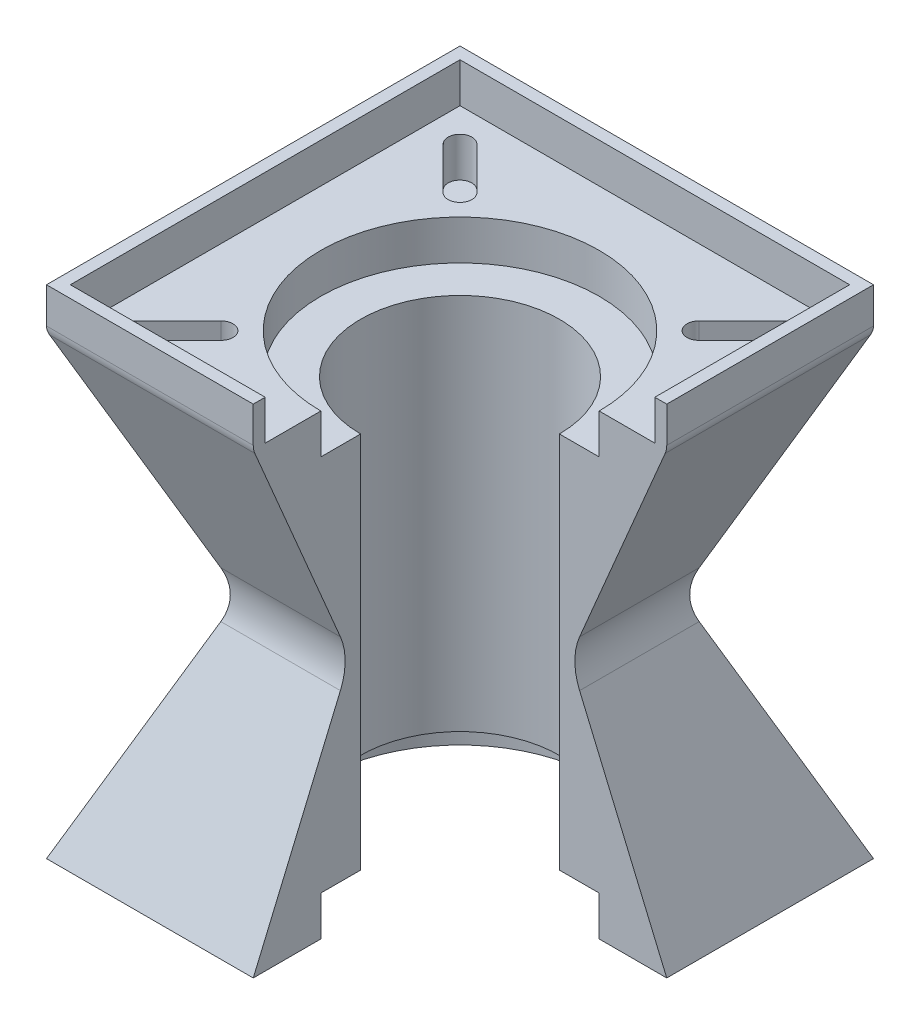
SolidWorks part; units mm, degrees
material "Cast Stainless Steel"
ref_plane "Front Plane" through (0, 0, 0) normal (0, 0, 1) x (1, 0, 0)
ref_plane "Top Plane" through (0, 0, 0) normal (0, 1, 0) x (1, 0, 0)
ref_plane "Right Plane" through (0, 0, 0) normal (1, 0, 0) x (0, 0, -1)
sketch "Sketch2" plane through (0, 0, 0) normal (0, 1, 0) x (1, 0, 0)
  line L1 (-52, -52) -> (52, -52)
  line L2 (-52, -52) -> (-52, 52)
  line L3 (-52, 52) -> (52, 52)
  line L4 (52, -52) -> (52, 52)
  line L5 (-52, -52) -> (52, 52) construction
  line L6 (-52, 52) -> (52, -52) construction
  point P0 (0, 0)
  dimension "D1" = 104
  dimension "D2" = 104
extrude "Boss-Extrude1" add sketch "Sketch2" along normal blind 57.5 draft 23
mirror "Mirror1" about plane through (0, 57.5, 0) normal (0, -1, 0) of "Boss-Extrude1"
sketch "Sketch3" plane through (0, 115, 0) normal (0, 1, 0) x (1, 0, 0)
  circle A0 centre (0, 0) radius 25
  dimension "D1" = 50
extrude "Cut-Extrude1" cut sketch "Sketch3" against normal through all
sketch "Sketch4" plane through (0, 115, 0) normal (0, 1, 0) x (1, 0, 0)
  circle A0 centre (0, 0) radius 35
  dimension "D1" = 70
extrude "Cut-Extrude2" cut sketch "Sketch4" against normal blind 10
ref_plane "Plane1" through (0, 57.5, 0) normal (0, 1, 0) x (1, 0, 0)
mirror "Mirror2" about plane through (0, 57.5, 0) normal (0, 1, 0) of "Cut-Extrude2"
sketch "Sketch6" plane through (0, 115, 0) normal (0, 1, 0) x (1, 0, 0)
  line L1 (0, 0) -> (52, 0)
  line L2 (0, 0) -> (0, -52)
  line L3 (0, -52) -> (52, -52)
  line L4 (52, 0) -> (52, -52)
extrude "Cut-Extrude3" cut sketch "Sketch6" against normal through all
fillet "Fillet1" radius 15 4 edges at (0, 57.5, -27.5927) (-27.5927, 57.5, 0) (27.5927, 57.5, -13.7963) (-13.7963, 57.5, 27.5927)
sketch "Sketch7" plane through (0, 115, 0) normal (0, 1, 0) x (1, 0, 0)
  line L6 (0, -52) -> (0, -35)
  line L7 (35, 0) -> (52, 0)
  line L8 (52, 0) -> (52, 52)
  line L9 (52, 52) -> (-52, 52)
  line L10 (-52, 52) -> (-52, -52)
  line L11 (-52, -52) -> (0, -52)
  line L12 (0, -52) -> (0, -49)
  line L14 (52, 0) -> (52, 52)
  line L15 (52, 52) -> (-52, 52)
  line L16 (-52, 52) -> (-52, -52)
  line L17 (-52, -52) -> (0, -52)
  line L18 (49, 0) -> (49, 49)
  line L19 (49, 49) -> (-49, 49)
  line L20 (-49, 49) -> (-49, -49)
  line L21 (-49, -49) -> (0, -49)
  line L22 (49, 0) -> (52, 0)
  arc A1 (35, 0) -> (0, -35) centre (0, 0) ccw
  arc A2 (35, 0) -> (0, -35) centre (0, 0) ccw
  dimension "D1" = 0
  dimension "D2" = 3
extrude "Boss-Extrude2" add sketch "Sketch7" along normal blind 10 contours L20 L21 L12 L17 L16 L15 L14 L22 L18 L19
fillet "Fillet2" radius 5 4 edges at (52, 115, -26) (0, 115, -52) (-52, 115, 0) (-26, 115, 52)
sketch "Sketch8" plane through (0, 115, 0) normal (0, 1, 0) x (1, 0, 0)
  line L0 (0, 0) -> (-52, 52) construction
  line L1 (0, 0) -> (52, 52) construction
  line L2 (0, 0) -> (-52, -52) construction
  line L3 (-30.052, 30.052) -> (-40.6586, 40.6586) construction
  line L4 (30.052, 30.052) -> (40.6586, 40.6586) construction
  line L5 (-32.1734, 27.9307) -> (-42.78, 38.5373)
  line L6 (-27.9307, 32.1734) -> (-38.5373, 42.78)
  line L7 (27.9307, 32.1734) -> (38.5373, 42.78)
  line L8 (32.1734, 27.9307) -> (42.78, 38.5373)
  line L12 (-30.052, -30.052) -> (-40.6586, -40.6586) construction
  line L13 (-27.9307, -32.1734) -> (-38.5373, -42.78)
  line L14 (-32.1734, -27.9307) -> (-42.78, -38.5373)
  line L18 (30.052, -30.052) -> (40.6586, -40.6586) construction
  line L19 (32.1734, -27.9307) -> (42.78, -38.5373)
  line L20 (27.9307, -32.1734) -> (38.5373, -42.78)
  line L21 (30.052, -30.052) -> (40.6586, -40.6586) construction
  line L22 (32.1734, -27.9307) -> (42.78, -38.5373)
  line L23 (27.9307, -32.1734) -> (38.5373, -42.78)
  circle A0 centre (0, 0) radius 50 construction
  arc A1 (-32.1734, 27.9307) -> (-27.9307, 32.1734) centre (-30.052, 30.052) ccw
  arc A2 (-38.5373, 42.78) -> (-42.78, 38.5373) centre (-40.6586, 40.6586) ccw
  arc A3 (27.9307, 32.1734) -> (32.1734, 27.9307) centre (30.052, 30.052) ccw
  arc A4 (42.78, 38.5373) -> (38.5373, 42.78) centre (40.6586, 40.6586) ccw
  arc A7 (-27.9307, -32.1734) -> (-32.1734, -27.9307) centre (-30.052, -30.052) ccw
  arc A8 (-42.78, -38.5373) -> (-38.5373, -42.78) centre (-40.6586, -40.6586) ccw
  arc A13 (32.1734, -27.9307) -> (27.9307, -32.1734) centre (30.052, -30.052) ccw
  arc A14 (38.5373, -42.78) -> (42.78, -38.5373) centre (40.6586, -40.6586) ccw
  point P12 (34.9972, 27.093)
  point P13 (-35.3553, 35.3553)
  point P20 (35.3553, 35.3553)
  point P34 (-35.3553, -35.3553)
  point P39 (0, 0)
  point P41 (35.3553, -35.3553)
  point P48 (35.3553, -35.3553)
  point P55 (35.3553, -35.3553)
  dimension "D1" = 100
  dimension "D3" = 3
  dimension "D2" = 15
  dimension "D4" = 4
extrude "Cut-Extrude4" cut sketch "Sketch8" against normal blind 10
equation "\"a\"= 115mm"
equation "\"b\"= 104mm"
equation "\"c\"= 23mm"
